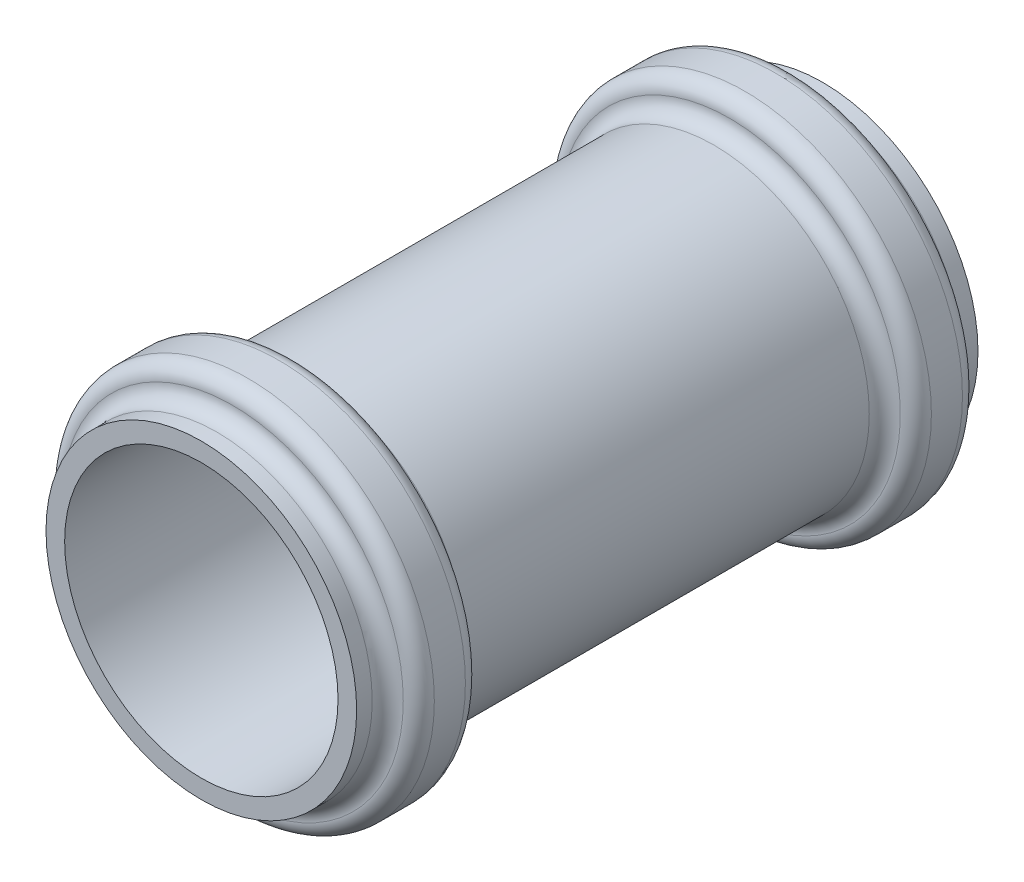
SolidWorks part; units mm, degrees
ref_plane "Спереди" through (0, 0, 0) normal (0, 0, 1) x (1, 0, 0)
ref_plane "Сверху" through (0, 0, 0) normal (0, 1, 0) x (1, 0, 0)
ref_plane "Справа" through (0, 0, 0) normal (1, 0, 0) x (0, 0, -1)
sketch "Эскиз1" plane through (0, 0, 0) normal (0, 0, 1) x (1, 0, 0)
  circle A0 centre (0, 0) radius 25
  circle A1 centre (0, 0) radius 22
  dimension "D1" = 50
  dimension "D2" = 3
extrude "Бобышка-Вытянуть1" add sketch "Эскиз1" along normal blind 100
sketch "Эскиз2" plane through (0, 0, 100) normal (0, 0, 1) x (1, 0, 0)
  circle A2 centre (0, 0) radius 30
  circle A3 centre (0, 0) radius 30
  circle M2 centre (0, 0) radius 25
  dimension "D1" = 5
extrude "Бобышка-Вытянуть2" add sketch "Эскиз2" against normal blind 10 from offset 5 contours A3 M2 region at (-29.1515, 0, 100) offset against normal yes
ref_plane "Плоскость4" through (0, 0, 50) normal (0, 0, 1) x (1, 0, 0)
fillet "Скругление1" radius 2.5 4 edges at (30, 0, 85) (25, 0, 85) (30, 0, 95) (25, 0, 95)
mirror "Зеркальное отражение1" about plane through (0, 0, 50) normal (0, 0, 1) of "Скругление1", "Бобышка-Вытянуть2"
